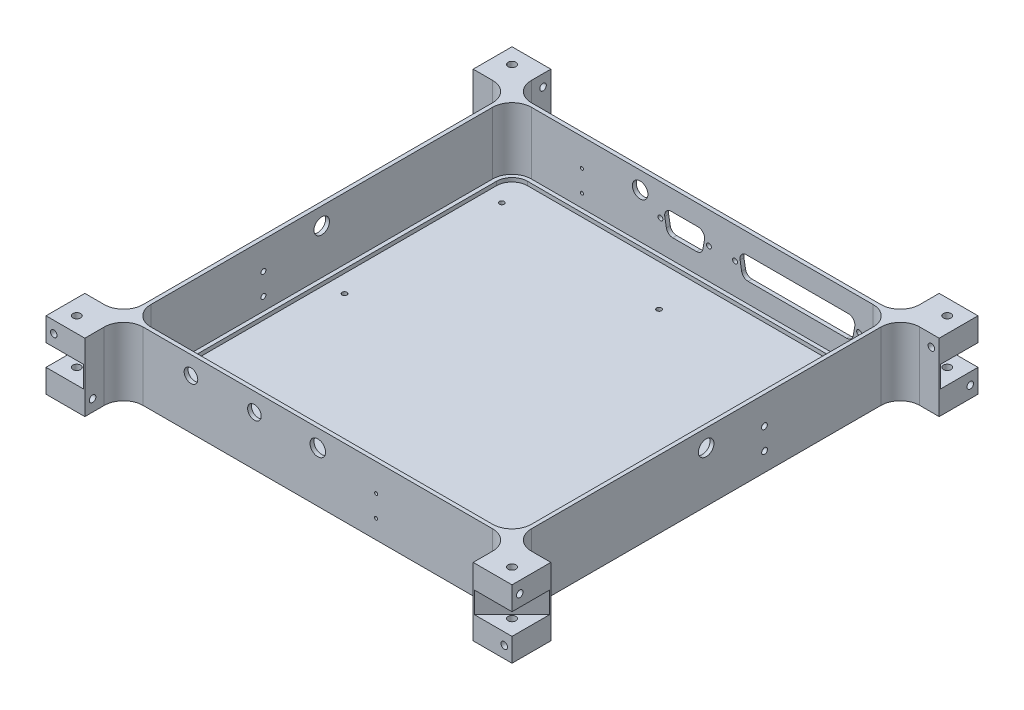
SolidWorks part; units mm, degrees
ref_plane "Front" through (0, 0, 0) normal (0, 0, 1) x (1, 0, 0)
ref_plane "Top" through (0, 0, 0) normal (0, 1, 0) x (1, 0, 0)
ref_plane "Right" through (0, 0, 0) normal (1, 0, 0) x (0, 0, -1)
sketch "Sketch1" plane through (0, 0, 0) normal (0, 1, 0) x (1, 0, 0)
  line L0 (-100, 90) -> (-100, -90)
  line L1 (-120, 120) -> (120, 120)
  line L2 (-120, 120) -> (-120, -120)
  line L3 (-120, -120) -> (120, -120)
  line L4 (120, 120) -> (120, -120)
  line L5 (-120, 120) -> (-100, 120)
  line L6 (-120, 120) -> (-120, 100)
  line L7 (-120, 100) -> (-110, 100)
  line L8 (-100, 120) -> (-100, 110)
  line L9 (-90, 100) -> (90, 100)
  line L10 (0, -24.5091) -> (0, 24.5091) construction
  line L11 (24.4282, 0) -> (-24.4282, 0) construction
  line L12 (100, 90) -> (100, -90)
  line L13 (100, 120) -> (100, 110)
  line L14 (120, 100) -> (110, 100)
  line L15 (120, 120) -> (120, 100)
  line L16 (120, 120) -> (100, 120)
  line L17 (120, -120) -> (100, -120)
  line L18 (120, -120) -> (120, -100)
  line L19 (120, -100) -> (110, -100)
  line L20 (100, -120) -> (100, -110)
  line L21 (-90, -100) -> (90, -100)
  line L22 (-100, -120) -> (-100, -110)
  line L23 (-120, -100) -> (-110, -100)
  line L24 (-120, -120) -> (-120, -100)
  line L25 (-120, -120) -> (-100, -120)
  line L26 (-120, -120) -> (120, -120)
  arc A0 (-100, 110) -> (-90, 100) centre (-90, 110) ccw
  arc A1 (-100, 90) -> (-110, 100) centre (-110, 90) ccw
  arc A2 (100, 90) -> (110, 100) centre (110, 90) cw
  arc A3 (100, 110) -> (90, 100) centre (90, 110) cw
  arc A4 (100, -110) -> (90, -100) centre (90, -110) ccw
  arc A5 (100, -90) -> (110, -100) centre (110, -90) ccw
  arc A6 (-100, -90) -> (-110, -100) centre (-110, -90) cw
  arc A7 (-100, -110) -> (-90, -100) centre (-90, -110) cw
  point P13 (0, -100)
  point P26 (0, 100)
  point P29 (0, 0)
  point P43 (100, 0)
  point P45 (-100, 0)
  dimension "D7" = 20
  dimension "D8" = 20
  dimension "D2" = 120
  dimension "D4" = 120
extrude "Boss-Extrude1" add sketch "Sketch1" along normal mid plane 35 contours L22 A7 L21 A4 L20 L3 L4 L19 A5 L12 A2 L14 L1 L13 A3 L9 A0 L8 L2 L7 A1 L0 A6 L23 region at (0, 0, 0)
sketch "Sketch3" plane through (0, 17.5, 0) normal (0, 1, 0) x (1, 0, 0)
  line L22 (-90, 100) -> (90, 100) construction
  line L23 (-88, 98) -> (88, 98)
  line L24 (-98, 88) -> (-98, -88)
  line L25 (-88, -98) -> (88, -98)
  line L26 (98, 88) -> (98, -88)
  line L27 (100, 90) -> (100, -90) construction
  line L28 (-90, -100) -> (90, -100) construction
  line L29 (-100, 90) -> (-100, -90) construction
  arc A0 (-98, -88) -> (-88, -98) centre (-88, -88) ccw
  arc A1 (88, -98) -> (98, -88) centre (88, -88) ccw
  arc A2 (88, 98) -> (98, 88) centre (88, 88) cw
  arc A3 (-88, 98) -> (-98, 88) centre (-88, 88) ccw
  dimension "D5" = 10
  dimension "D1" = 2
  dimension "D2" = 2
  dimension "D3" = 2
  dimension "D4" = 2
extrude "Cut-Extrude1" cut sketch "Sketch3" against normal blind 32
sketch "Sketch4" plane through (0, -14.5, 0) normal (0, 1, 0) x (1, 0, 0)
  line L8 (-88, -96) -> (88, -96)
  line L9 (96, -88) -> (96, 88)
  line L10 (88, 96) -> (-88, 96)
  line L11 (-96, 88) -> (-96, -88)
  line L12 (-88, -96) -> (88, -96)
  line L13 (96, -88) -> (96, 88)
  line L14 (88, 96) -> (-88, 96)
  line L15 (-96, 88) -> (-96, -88)
  arc A8 (-96, -88) -> (-88, -96) centre (-88, -88) ccw
  arc A9 (88, -96) -> (96, -88) centre (88, -88) ccw
  arc A10 (96, 88) -> (88, 96) centre (88, 88) ccw
  arc A11 (-88, 96) -> (-96, 88) centre (-88, 88) ccw
  arc A12 (-96, -88) -> (-88, -96) centre (-88, -88) ccw
  arc A13 (88, -96) -> (96, -88) centre (88, -88) ccw
  arc A14 (96, 88) -> (88, 96) centre (88, 88) ccw
  arc A15 (-88, 96) -> (-96, 88) centre (-88, 88) ccw
  dimension "D1" = 2
extrude "Cut-Extrude2" cut sketch "Sketch4" against normal blind 2
sketch "Sketch5" plane through (0, -17.5, 0) normal (0, -1, 0) x (1, 0, 0)
  line L23 (98, -88) -> (98, 88)
  line L24 (-88, -98) -> (88, -98)
  line L25 (-98, 88) -> (-98, -88)
  line L26 (88, 98) -> (-88, 98)
  line L27 (98, -88) -> (98, 88)
  line L28 (-88, -98) -> (88, -98)
  line L29 (-98, 88) -> (-98, -88)
  line L30 (88, 98) -> (-88, 98)
  arc A21 (98, 88) -> (88, 98) centre (88, 88) ccw
  arc A22 (88, -98) -> (98, -88) centre (88, -88) ccw
  arc A23 (-98, -88) -> (-88, -98) centre (-88, -88) ccw
  arc A24 (-88, 98) -> (-98, 88) centre (-88, 88) ccw
  arc A25 (98, 88) -> (88, 98) centre (88, 88) ccw
  arc A26 (88, -98) -> (98, -88) centre (88, -88) ccw
  arc A27 (-98, -88) -> (-88, -98) centre (-88, -88) ccw
  arc A28 (-88, 98) -> (-98, 88) centre (-88, 88) ccw
  dimension "D1" = 0
extrude "Boss-Extrude2" add sketch "Sketch5" along normal blind 2
ref_plane "Plane1" through (0, 5.5, 0) normal (0, 1, 0) x (1, 0, 0)
sketch "Sketch6" plane through (0, 5.5, 0) normal (0, 1, 0) x (1, 0, 0)
  line L0 (0, 0) -> (-112.0764, 112.0764) construction
  line L1 (-112.0764, 112.0764) -> (-112.0764, 0) construction
  line L2 (-112.0764, 0) -> (0, 0) construction
  line L3 (-120, 100.6173) -> (-100.6173, 120)
  line L4 (-120, 120) -> (-120, 100) construction
  line L5 (-120, 120) -> (-100, 120) construction
  line L6 (-120, 100.6173) -> (-120, 120)
  line L7 (-120, 120) -> (-100, 120)
  circle A0 centre (-112.0764, 112.0764) radius 2
  dimension "D2" = 4
  dimension "D1" = 158.5
  dimension "D3" = 2.5
  dimension "D4" = 135
extrude "Cut-Extrude3" cut sketch "Sketch6" against normal blind 11 contours L7 L6 L3 A0 | A0 region at (-113.644, 5.5, -113.644)
ref_axis "Axis1" through (0, 0, 0) along (0, 1, 0)
pattern_circular "CirPattern1" count 4 every 90 about axis through (0, 0, 0) along (0, 1, 0) of "Cut-Extrude3"
sketch "Sketch7" plane through (120, 0, 0) normal (1, 0, 0) x (0, 0, -1)
  line L0 (-120, 17.5) -> (-120, 5.5) construction
  line L1 (-100, 17.5) -> (-120, 17.5) construction
  line L2 (120, -17.5) -> (100, -17.5) construction
  line L3 (120, -5.5) -> (120, -17.5) construction
  point P0 (-116, 11.5)
  point P1 (116, -11.5)
  dimension "D1" = 4
  dimension "D2" = 6
  dimension "D3" = 6
  dimension "D4" = 4
sketch "Sketch8" plane through (-120, 0, 0) normal (-1, 0, 0) x (0, 0, 1)
  line L0 (-120, 17.5) -> (-120, 5.5) construction
  line L1 (-120, 17.5) -> (-100, 17.5) construction
  line L2 (100, -17.5) -> (120, -17.5) construction
  line L3 (120, -5.5) -> (120, -17.5) construction
  point P0 (-116, 11.5)
  point P1 (116, -11.5)
  dimension "D1" = 4
  dimension "D2" = 6
  dimension "D3" = 6
  dimension "D4" = 4
sketch "Sketch9" plane through (0, 0, 120) normal (0, 0, 1) x (1, 0, 0)
  line L0 (-120, 17.5) -> (-120, 5.5) construction
  line L1 (-120, 17.5) -> (-100, 17.5) construction
  line L2 (100, -17.5) -> (120, -17.5) construction
  line L3 (120, -5.5) -> (120, -17.5) construction
  point P0 (-116, 11.5)
  point P1 (116, -11.5)
  dimension "D1" = 4
  dimension "D2" = 6
  dimension "D3" = 6
  dimension "D4" = 4
sketch "Sketch10" plane through (0, 0, -120) normal (0, 0, -1) x (-1, 0, 0)
  line L1 (-120, 17.5) -> (-120, 5.5) construction
  line L2 (-100, 17.5) -> (-120, 17.5) construction
  line L3 (120, -17.5) -> (100, -17.5) construction
  line L4 (120, -5.5) -> (120, -17.5) construction
  point P0 (-116, 11.5)
  point P1 (116, -11.5)
  dimension "D1" = 6
  dimension "D2" = 4
  dimension "D3" = 6
  dimension "D4" = 4
hole_wizard "M3 Clearance Hole1" positions "3DSketch1" profile "Sketch11" hole size "M3" standard "AS"
sketch3d "3DSketch1"
  point P0 (116, 11.5, -120)
  point P3 (120, 11.5, 116)
  point P6 (-116, -11.5, -120)
  point P9 (-120, 11.5, -116)
  point P12 (-120, -11.5, 116)
  point P15 (-116, 11.5, 120)
  point P18 (116, -11.5, 120)
  point P21 (120, -11.5, -116)
sketch "Sketch11" plane through (116, 11.5, -120) normal (1, 0, 0) x (0, 1, 0)
  line L0 (0, 0) -> (0, 21.0215)
  line L1 (0, 21.0215) -> (1.7, 20)
  line L2 (1.7, 20) -> (1.7, 0)
  line L5 (1.7, 0) -> (0, 0)
  line L10 (0, 21.0215) -> (-1.7, 20) construction
  line L11 (0, -6.35) -> (0, 107.95) construction
  dimension "Hole Dia." = 3.4
  dimension "Hole Depth" = 20
  dimension "Drill Angle" = 118
sketch "Sketch12" plane through (100, 0, 0) normal (1, 0, 0) x (0, 0, -1)
  line L0 (88, -17.5) -> (-88, -17.5) construction
  line L1 (90, -17.5) -> (-90, -17.5) construction
  circle A0 centre (0, 8.6) radius 4
  circle A1 centre (30, 3.25) radius 1.5
  circle A2 centre (30.0773, -7.85) radius 1.5
  point P6 (0, 0)
  dimension "D1" = 8
  dimension "D6" = 3
  dimension "D7" = 3
  dimension "D2" = 26.1
  dimension "D3" = 30
  dimension "D4" = 11.1
  dimension "D5" = 9.65
extrude "Cut-Extrude4" cut sketch "Sketch12" against normal up to next
sketch "Sketch13" plane through (0, 17.5, 0) normal (0, 1, 0) x (1, 0, 0)
  line L0 (0, 0) -> (-125.5307, 125.5307) construction
  line L1 (-120, 100.6173) -> (-100.6173, 120)
  line L2 (-120, 120) -> (-120, 100) construction
  line L3 (-120, 120) -> (-100, 120) construction
  circle A0 centre (-112.0764, 112.0764) radius 2
  dimension "D2" = 4
  dimension "D1" = 158.5
  dimension "D3" = 2.5
  dimension "D4" = 135
extrude "Cut-Extrude5" cut sketch "Sketch13" against normal through all contours L0 A0 | A0 L0 region at (-112.6766, 17.5, -111.4762) region at (-111.4762, 17.5, -112.6766)
pattern_circular "CirPattern2" count 4 every 90 about axis through (0, 0, 0) along (0, 1, 0) of "Cut-Extrude5"
hole_wizard "M3x0.5 Tapped Hole1" positions "Sketch20" profile "Sketch19" tap size "M3x0.5" standard "ANSI Metric"
sketch "Sketch20" plane through (0, -16.5, 0) normal (0, 1, 0) x (1, 0, 0)
  line L0 (96, -88) -> (96, 88) construction
  line L2 (-96, 88) -> (-96, -88) construction
  line L3 (96, -88) -> (96, 88) construction
  line L4 (88, 96) -> (-88, 96) construction
  line L5 (88, 96) -> (-88, 96) construction
  line L6 (-88, -96) -> (88, -96) construction
  point P0 (-87, 81.75)
  point P2 (1, 74.75)
  point P4 (83, 88.75)
  point P6 (87, 0.75)
  point P8 (87, -87.25)
  point P10 (0, -87.25)
  point P12 (-87, -87.25)
  point P14 (-87, 0.75)
  dimension "D1" = 95
  dimension "D2" = 13
  dimension "D3" = 9
  dimension "D4" = 9
  dimension "D5" = 9
  dimension "D6" = 96
  dimension "D7" = 9
  dimension "D8" = 9
  dimension "D9" = 7.25
  dimension "D10" = 21.25
  dimension "D11" = 14.25
  dimension "D12" = 95.25
  dimension "D13" = 95.25
  dimension "D14" = 8.75
  dimension "D15" = 8.75
  dimension "D16" = 8.75
sketch "Sketch19" plane through (-87, -16.5, -81.75) normal (1, 0, 0) x (0, 0, 1)
  line L0 (0, 0) -> (0, 5.7511)
  line L1 (0, 5.7511) -> (1.25, 5)
  line L2 (1.25, 5) -> (1.25, 0)
  line L5 (1.25, 0) -> (0, 0)
  line L10 (0, 5.7511) -> (-1.25, 5) construction
  line L11 (0, -6.35) -> (0, 107.95) construction
  dimension "Tap Drill Dia." = 2.5
  dimension "Tap Drill Depth" = 5
  dimension "Drill Angle" = 118
cosmetic thread "Hole Thread1" parameters "D1"=3, "D2"=3
cosmetic thread "Hole Thread2" parameters "D1"=3, "D2"=3
cosmetic thread "Hole Thread3" parameters "D1"=3, "D2"=3
cosmetic thread "Hole Thread4" parameters "D1"=3, "D2"=3
cosmetic thread "Hole Thread5" parameters "D1"=3, "D2"=3
cosmetic thread "Hole Thread6" parameters "D1"=3, "D2"=3
cosmetic thread "Hole Thread7" parameters "D1"=3, "D2"=3
cosmetic thread "Hole Thread8" parameters "D1"=3, "D2"=3
sketch "Sketch21" plane through (-100, 0, 0) normal (-1, 0, 0) x (0, 0, 1)
  line L1 (-90, -17.5) -> (90, -17.5) construction
  line L2 (-90, 17.5) -> (-90, -17.5) construction
  circle A0 centre (0, 8.6) radius 4
  dimension "D1" = 8
  dimension "D2" = 26.1
  dimension "D3" = 90
extrude "Cut-Extrude6" cut sketch "Sketch21" against normal blind 10
hole_wizard "M3x0.5 Tapped Hole2" positions "Sketch23" profile "Sketch22" tap size "M3x0.5" standard "ANSI Metric"
sketch "Sketch23" plane through (-100, 0, 0) normal (-1, 0, 0) x (0, 0, 1)
  line L0 (88, -17.5) -> (-88, -17.5) construction
  circle A0 centre (0, 8.6) radius 4 construction
  point P0 (30, 3.25)
  point P2 (30, -7.85)
  dimension "D1" = 30
  dimension "D2" = 30
  dimension "D3" = 9.65
  dimension "D4" = 11.1
sketch "Sketch22" plane through (-100, 3.25, 30) normal (0, 1, 0) x (0, 0, 1)
  line L0 (0, 0) -> (0, 5.7511)
  line L1 (0, 5.7511) -> (1.25, 5)
  line L2 (1.25, 5) -> (1.25, 0)
  line L5 (1.25, 0) -> (0, 0)
  line L10 (0, 5.7511) -> (-1.25, 5) construction
  line L11 (0, -6.35) -> (0, 107.95) construction
  dimension "Tap Drill Dia." = 2.5
  dimension "Tap Drill Depth" = 5
  dimension "Drill Angle" = 118
cosmetic thread "Hole Thread9" parameters "D1"=2, "D2"=3
cosmetic thread "Hole Thread10" parameters "D1"=2, "D2"=3
sketch "Sketch24" plane through (0, 0, 100) normal (0, 0, 1) x (1, 0, 0)
  line L0 (88, -17.5) -> (-88, -17.5) construction
  line L1 (90, 17.5) -> (90, -17.5) construction
  line L2 (-90, -17.5) -> (90, -17.5) construction
  circle A0 centre (0, 8.6) radius 4
  circle A1 centre (-32.67, 8.1) radius 3.5
  circle A2 centre (-65.34, 8.1) radius 3.5
  dimension "D1" = 8
  dimension "D4" = 7
  dimension "D6" = 25.6
  dimension "D7" = 7
  dimension "D2" = 26.1
  dimension "D3" = 90
  dimension "D5" = 32.67
  dimension "D8" = 32.67
  dimension "D9" = 25.6
extrude "Cut-Extrude7" cut sketch "Sketch24" against normal blind 10
hole_wizard "M2x0.4 Tapped Hole1" positions "Sketch27" profile "Sketch25" tap size "M2x0.4" standard "ANSI Metric"
sketch "Sketch27" plane through (0, 0, 100) normal (0, 0, 1) x (1, 0, 0)
  line L0 (-90, -17.5) -> (90, -17.5) construction
  circle A0 centre (0, 8.6) radius 4 construction
  point P0 (30, 3.25)
  point P2 (30, -7.85)
  dimension "D1" = 30
  dimension "D2" = 30
  dimension "D3" = 11.1
  dimension "D4" = 9.65
sketch "Sketch25" plane through (30, 3.25, 100) normal (1, 0, 0) x (0, -1, 0)
  line L0 (0, 0) -> (0, 5.6807)
  line L1 (0, 5.6807) -> (0.8, 5.2)
  line L2 (0.8, 5.2) -> (0.8, 0)
  line L5 (0.8, 0) -> (0, 0)
  line L10 (0, 5.6807) -> (-0.8, 5.2) construction
  line L11 (0, -6.35) -> (0, 107.95) construction
  dimension "Tap Drill Dia." = 1.6
  dimension "Tap Drill Depth" = 5.2
  dimension "Drill Angle" = 118
cosmetic thread "Hole Thread11" parameters "D1"=2, "D2"=2
cosmetic thread "Hole Thread12" parameters "D1"=2, "D2"=2
sketch "Sketch28" plane through (0, 0, -100) normal (0, 0, -1) x (-1, 0, 0)
  line L0 (2.1541, 7.07) -> (16.0259, 7.07)
  line L1 (19.325, 3.1383) -> (18.4963, -1.5617)
  line L2 (15.1972, -4.33) -> (2.9828, -4.33)
  line L3 (-0.3163, -1.5617) -> (-1.145, 3.1383)
  line L4 (90, -17.5) -> (-90, -17.5) construction
  line L5 (90, 17.5) -> (90, -17.5) construction
  line L6 (-75.2409, 7.07) -> (-22.7591, 7.07)
  line L7 (-19.46, 3.1383) -> (-20.2887, -1.5617)
  line L8 (-23.5878, -4.33) -> (-74.4122, -4.33)
  line L9 (-77.7113, -1.5617) -> (-78.54, 3.1383)
  line L10 (-90, 17.5) -> (-90, -17.5) construction
  line L11 (88, -17.5) -> (-88, -17.5) construction
  arc A0 (16.0259, 7.07) -> (19.325, 3.1383) centre (16.0259, 3.72) cw
  arc A1 (18.4963, -1.5617) -> (15.1972, -4.33) centre (15.1972, -0.98) cw
  arc A2 (2.9828, -4.33) -> (-0.3163, -1.5617) centre (2.9828, -0.98) cw
  arc A3 (-1.145, 3.1383) -> (2.1541, 7.07) centre (2.1541, 3.72) cw
  arc A4 (-22.7591, 7.07) -> (-19.46, 3.1383) centre (-22.7591, 3.72) cw
  arc A5 (-20.2887, -1.5617) -> (-23.5878, -4.33) centre (-23.5878, -0.98) cw
  arc A6 (-74.4122, -4.33) -> (-77.7113, -1.5617) centre (-74.4122, -0.98) cw
  arc A7 (-78.54, 3.1383) -> (-75.2409, 7.07) centre (-75.2409, 3.72) cw
  circle A8 centre (32, 8.6) radius 4
  dimension "D1" = 3.35
  dimension "D2" = 3.35
  dimension "D3" = 3.35
  dimension "D4" = 3.35
  dimension "D11" = 3.35
  dimension "D12" = 3.35
  dimension "D13" = 3.35
  dimension "D14" = 3.35
  dimension "D20" = 8
  dimension "D21" = 58
  dimension "D22" = 26.1
  dimension "D5" = 11.4
  dimension "D6" = 20.47
  dimension "D7" = 80
  dimension "D8" = 80
  dimension "D9" = 13.17
  dimension "D10" = 70.675
  dimension "D15" = 11.4
  dimension "D16" = 80
  dimension "D17" = 80
  dimension "D18" = 59.08
  dimension "D19" = 11.46
extrude "Cut-Extrude8" cut sketch "Sketch28" against normal blind 10
hole_wizard "M3x0.5 Tapped Hole3" positions "Sketch30" profile "Sketch29" tap size "M3x0.5" standard "ANSI Metric"
sketch "Sketch30" plane through (0, 0, -100) normal (0, 0, -1) x (-1, 0, 0)
  line L0 (16.0259, 7.07) -> (2.1541, 7.07) construction
  line L1 (-22.7591, 7.07) -> (-75.2409, 7.07) construction
  point P0 (-80.75, 1.36)
  point P2 (-16.85, 1.36)
  point P4 (-3.405, 1.36)
  point P6 (21.585, 1.36)
  dimension "D1" = 2.26
  dimension "D2" = 2.26
  dimension "D3" = 5.71
  dimension "D4" = 5.71
  dimension "D5" = 5.71
  dimension "D6" = 5.71
  dimension "D7" = 2.21
  dimension "D8" = 2.61
sketch "Sketch29" plane through (80.75, 1.36, -100) normal (1, 0, 0) x (0, 1, 0)
  line L0 (0, 0) -> (0, 8.2511)
  line L1 (0, 8.2511) -> (1.25, 7.5)
  line L2 (1.25, 7.5) -> (1.25, 0)
  line L5 (1.25, 0) -> (0, 0)
  line L10 (0, 8.2511) -> (-1.25, 7.5) construction
  line L11 (0, -6.35) -> (0, 107.95) construction
  dimension "Tap Drill Dia." = 2.5
  dimension "Tap Drill Depth" = 7.5
  dimension "Drill Angle" = 118
cosmetic thread "Hole Thread13" parameters "D1"=2, "D2"=3
cosmetic thread "Hole Thread14" parameters "D1"=2, "D2"=3
cosmetic thread "Hole Thread15" parameters "D1"=2, "D2"=3
cosmetic thread "Hole Thread16" parameters "D1"=2, "D2"=3
hole_wizard "M2x0.4 Tapped Hole2" positions "Sketch32" profile "Sketch31" tap size "M2x0.4" standard "ANSI Metric"
sketch "Sketch32" plane through (0, 0, -100) normal (0, 0, -1) x (-1, 0, 0)
  line L0 (90, -17.5) -> (-90, -17.5) construction
  line L1 (90, 17.5) -> (90, -17.5) construction
  point P0 (62, 3.25)
  point P2 (62, -7.85)
  dimension "D1" = 9.65
  dimension "D2" = 11.1
  dimension "D3" = 28
  dimension "D4" = 28
sketch "Sketch31" plane through (-62, 3.25, -100) normal (1, 0, 0) x (0, 1, 0)
  line L0 (0, 0) -> (0, 5.6807)
  line L1 (0, 5.6807) -> (0.8, 5.2)
  line L2 (0.8, 5.2) -> (0.8, 0)
  line L5 (0.8, 0) -> (0, 0)
  line L10 (0, 5.6807) -> (-0.8, 5.2) construction
  line L11 (0, -6.35) -> (0, 107.95) construction
  dimension "Tap Drill Dia." = 1.6
  dimension "Tap Drill Depth" = 5.2
  dimension "Drill Angle" = 118
cosmetic thread "Hole Thread17" parameters "D1"=2, "D2"=2
cosmetic thread "Hole Thread18" parameters "D1"=2, "D2"=2
